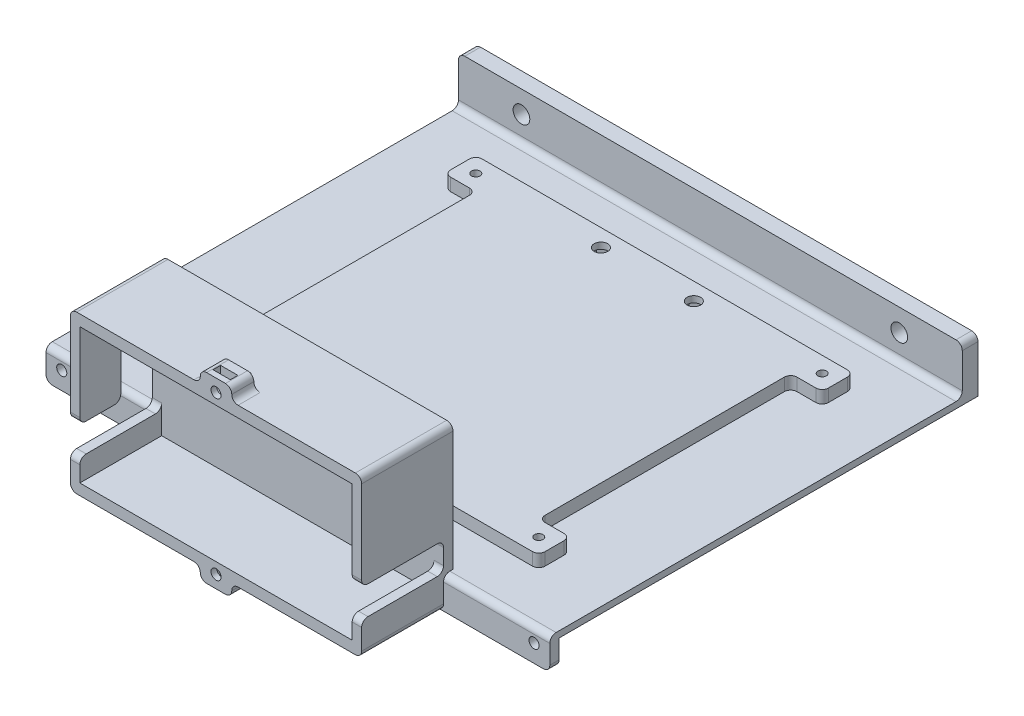
SolidWorks part; units mm, degrees
ref_plane "Front Plane" through (0, 0, 0) normal (0, 0, 1) x (1, 0, 0)
ref_plane "Top Plane" through (0, 0, 0) normal (0, 1, 0) x (1, 0, 0)
ref_plane "Right Plane" through (0, 0, 0) normal (1, 0, 0) x (0, 0, -1)
sketch "Sketch1" plane through (0, 0, 0) normal (0, 1, 0) x (1, 0, 0)
  line L1 (-80, -66.5) -> (80, -66.5)
  line L2 (-80, -66.5) -> (-80, 66.5)
  line L3 (-80, 66.5) -> (80, 66.5)
  line L4 (80, -66.5) -> (80, 66.5)
  line L5 (-80, -66.5) -> (80, 66.5) construction
  line L6 (-80, 66.5) -> (80, -66.5) construction
  point P0 (0, 0)
  dimension "D1" = 133
  dimension "D2" = 160
extrude "Boss-Extrude1" add sketch "Sketch1" along normal blind 2
sketch "Sketch2" plane through (0, 0, 66.5) normal (0, 0, 1) x (1, 0, 0)
  line L0 (75, -2.38) -> (-75, -2.38) construction
  line L1 (-80, 2) -> (80, 2)
  line L2 (-80, 2) -> (-80, -8)
  line L3 (-80, -8) -> (80, -8)
  line L4 (80, 2) -> (80, -8)
  line L6 (-80, 0) -> (80, 0) construction
  point P10 (0, -2.38)
  dimension "D1" = 2.38
  dimension "D2" = 150
  dimension "D3" = 10
extrude "Boss-Extrude2" add sketch "Sketch2" along normal blind 3
hole_wizard "M3 Clearance Hole1" positions "Sketch3" profile "Sketch4" hole size "M3" standard "ANSI Metric"
sketch "Sketch3" plane through (0, 0, 69.5) normal (0, 0, 1) x (1, 0, 0)
  point P0 (-75, -2.38)
  point P3 (75, -2.38)
sketch "Sketch4" plane through (-75, -2.38, 69.5) normal (1, 0, 0) x (0, -1, 0)
  line L0 (0, 0) -> (0, 13.3614)
  line L1 (0, 13.3614) -> (1.6, 12.4)
  line L2 (1.6, 12.4) -> (1.6, 0)
  line L5 (1.6, 0) -> (0, 0)
  line L10 (0, 13.3614) -> (-1.6, 12.4) construction
  line L11 (0, -6.35) -> (0, 107.95) construction
  dimension "Hole Dia." = 3.2
  dimension "Hole Depth" = 12.4
  dimension "Drill Angle" = 118
sketch "Sketch5" plane through (0, 0, -66.5) normal (0, 0, -1) x (-1, 0, 0)
  line L1 (-80, 2) -> (80, 2)
  line L2 (-80, 2) -> (-80, 17)
  line L3 (-80, 17) -> (80, 17)
  line L4 (80, 2) -> (80, 17)
  dimension "D1" = 15
extrude "Boss-Extrude3" add sketch "Sketch5" against normal blind 5
sketch "Sketch6" plane through (0, 0, -61.5) normal (0, 0, 1) x (1, 0, 0)
  line L0 (-60, 10) -> (60, 10) construction
  line L1 (80, 2) -> (-80, 2) construction
  point P1 (60, 10)
  point P2 (-60, 10)
  point P14 (0, 10)
  point P17 (-60, 10)
  point P19 (60, 10)
  dimension "D1" = 120
  dimension "D2" = 8
hole_wizard "M5 Clearance Hole1" positions "Sketch6" profile "Sketch7" hole size "M5" standard "ANSI Metric"
sketch "Sketch7" plane through (60, 10, -61.5) normal (1, 0, 0) x (0, -1, 0)
  line L0 (0, 0) -> (0, 13.9923)
  line L1 (0, 13.9923) -> (2.65, 12.4)
  line L2 (2.65, 12.4) -> (2.65, 0)
  line L5 (2.65, 0) -> (0, 0)
  line L10 (0, 13.9923) -> (-2.65, 12.4) construction
  line L11 (0, -6.35) -> (0, 107.95) construction
  dimension "Hole Dia." = 5.3
  dimension "Hole Depth" = 12.4
  dimension "Drill Angle" = 118
sketch "Sketch8" plane through (0, 2, 0) normal (0, 1, 0) x (1, 0, 0)
  line L0 (-50, 37) -> (-50, -43)
  line L1 (-14.75, -47.5) -> (14.75, -47.5) construction
  line L2 (-14.75, -47.5) -> (-14.75, 41.5) construction
  line L3 (-14.75, 41.5) -> (14.75, 41.5) construction
  line L4 (14.75, -47.5) -> (14.75, 41.5) construction
  line L5 (-14.75, -47.5) -> (14.75, 41.5) construction
  line L6 (-14.75, 41.5) -> (14.75, -47.5) construction
  line L7 (-50, -53) -> (50, -53)
  line L8 (-50, -53) -> (-50, 47) construction
  line L9 (-50, 47) -> (50, 47)
  line L10 (50, -53) -> (50, 47) construction
  line L11 (-50, -53) -> (50, 47) construction
  line L12 (-50, 47) -> (50, -53) construction
  line L13 (-50, 47) -> (-60, 47)
  line L14 (-50, 47) -> (-50, 37) construction
  line L15 (-50, 37) -> (-60, 37)
  line L16 (-60, 47) -> (-60, 37)
  line L17 (-50, -53) -> (-60, -53)
  line L18 (-50, -53) -> (-50, -43) construction
  line L19 (-50, -43) -> (-60, -43)
  line L20 (-60, -53) -> (-60, -43)
  line L21 (50, -53) -> (60, -53)
  line L22 (50, -53) -> (50, -43) construction
  line L23 (50, -43) -> (60, -43)
  line L24 (60, -53) -> (60, -43)
  line L25 (50, 47) -> (60, 47)
  line L26 (50, 47) -> (50, 37) construction
  line L27 (50, 37) -> (60, 37)
  line L28 (60, 47) -> (60, 37)
  line L29 (50, -43) -> (50, 37)
  line L31 (-55, -48) -> (55, -48) construction
  line L32 (-55, -48) -> (-55, 42) construction
  line L33 (-55, 42) -> (55, 42) construction
  line L34 (55, -48) -> (55, 42) construction
  line L35 (-55, -48) -> (55, 42) construction
  line L36 (-55, 42) -> (55, -48) construction
  point P0 (0, -3)
  point P5 (0, -3)
  point P6 (0, -3)
  dimension "D1" = 29.5
  dimension "D2" = 89
  dimension "D3" = 100
  dimension "D4" = 100
  dimension "D5" = 3
  dimension "D6" = 10
  dimension "D7" = 10
  dimension "D8" = 110
  dimension "D9" = 90
extrude "Boss-Extrude4" add sketch "Sketch8" along normal blind 4
hole_wizard "M2.5 Clearance Hole1" positions "Sketch23" profile "Sketch24" hole size "M2.5" standard "ANSI Metric" end condition through all
sketch "Sketch23" plane through (0, 6, 0) normal (0, 1, 0) x (1, 0, 0)
  point P0 (-55, 42)
  point P3 (55, 42)
  point P6 (55, -48)
  point P9 (-55, -48)
sketch "Sketch24" plane through (-55, 6, -42) normal (1, 0, 0) x (0, 0, 1)
  line L0 (0, 0) -> (0, 14)
  line L1 (0, 14) -> (1.35, 14)
  line L2 (1.35, 14) -> (1.35, 0)
  line L5 (1.35, 0) -> (0, 0)
  line L11 (0, -6.35) -> (0, 107.95) construction
  dimension "Thru Hole Dia." = 2.7
  dimension "Thru Hole Depth" = 14
hole_wizard "M4 Clearance Hole1" positions "Sketch9" profile "Sketch10" hole size "M4" standard "ANSI Metric" end condition through all
sketch "Sketch9" plane through (0, 6, 0) normal (0, 1, 0) x (1, 0, 0)
  point P0 (-14.75, 41.5)
  point P3 (14.75, 41.5)
  point P6 (-14.75, -47.5)
  point P9 (14.75, -47.5)
sketch "Sketch10" plane through (-14.75, 6, -41.5) normal (1, 0, 0) x (0, 0, 1)
  line L0 (0, 0) -> (0, 14)
  line L1 (0, 14) -> (2.15, 14)
  line L2 (2.15, 14) -> (2.15, 0)
  line L5 (2.15, 0) -> (0, 0)
  line L11 (0, -6.35) -> (0, 107.95) construction
  dimension "Thru Hole Dia." = 4.3
  dimension "Thru Hole Depth" = 14
sketch "Sketch25" plane through (0, 0, 0) normal (0, -1, 0) x (-1, 0, 0)
  line L1 (55, -50.8868) -> (57.5, -49.4434)
  line L2 (57.5, -49.4434) -> (57.5, -46.5566)
  line L3 (57.5, -46.5566) -> (55, -45.1132)
  line L4 (55, -45.1132) -> (52.5, -46.5566)
  line L5 (52.5, -46.5566) -> (52.5, -49.4434)
  line L6 (52.5, -49.4434) -> (55, -50.8868)
  line L7 (-55, -50.8868) -> (-52.5, -49.4434)
  line L8 (-52.5, -49.4434) -> (-52.5, -46.5566)
  line L9 (-52.5, -46.5566) -> (-55, -45.1132)
  line L10 (-55, -45.1132) -> (-57.5, -46.5566)
  line L11 (-57.5, -46.5566) -> (-57.5, -49.4434)
  line L12 (-57.5, -49.4434) -> (-55, -50.8868)
  line L13 (-55, 39.1132) -> (-52.5, 40.5566)
  line L14 (-52.5, 40.5566) -> (-52.5, 43.4434)
  line L15 (-52.5, 43.4434) -> (-55, 44.8868)
  line L16 (-55, 44.8868) -> (-57.5, 43.4434)
  line L17 (-57.5, 43.4434) -> (-57.5, 40.5566)
  line L18 (-57.5, 40.5566) -> (-55, 39.1132)
  line L19 (55, 39.1132) -> (57.5, 40.5566)
  line L20 (57.5, 40.5566) -> (57.5, 43.4434)
  line L21 (57.5, 43.4434) -> (55, 44.8868)
  line L22 (55, 44.8868) -> (52.5, 43.4434)
  line L23 (52.5, 43.4434) -> (52.5, 40.5566)
  line L24 (52.5, 40.5566) -> (55, 39.1132)
  line L25 (-14.75, 45.5415) -> (-18.25, 43.5207)
  line L26 (-18.25, 43.5207) -> (-18.25, 39.4793)
  line L27 (-18.25, 39.4793) -> (-14.75, 37.4585)
  line L28 (-14.75, 37.4585) -> (-11.25, 39.4793)
  line L29 (-11.25, 39.4793) -> (-11.25, 43.5207)
  line L30 (-11.25, 43.5207) -> (-14.75, 45.5415)
  line L31 (14.75, 45.5415) -> (11.25, 43.5207)
  line L32 (11.25, 43.5207) -> (11.25, 39.4793)
  line L33 (11.25, 39.4793) -> (14.75, 37.4585)
  line L34 (14.75, 37.4585) -> (18.25, 39.4793)
  line L35 (18.25, 39.4793) -> (18.25, 43.5207)
  line L36 (18.25, 43.5207) -> (14.75, 45.5415)
  line L37 (14.75, -43.4585) -> (11.25, -45.4793)
  line L38 (11.25, -45.4793) -> (11.25, -49.5207)
  line L39 (11.25, -49.5207) -> (14.75, -51.5415)
  line L40 (14.75, -51.5415) -> (18.25, -49.5207)
  line L41 (18.25, -49.5207) -> (18.25, -45.4793)
  line L42 (18.25, -45.4793) -> (14.75, -43.4585)
  line L43 (-14.75, -43.4585) -> (-18.25, -45.4793)
  line L44 (-18.25, -45.4793) -> (-18.25, -49.5207)
  line L45 (-18.25, -49.5207) -> (-14.75, -51.5415)
  line L46 (-14.75, -51.5415) -> (-11.25, -49.5207)
  line L47 (-11.25, -49.5207) -> (-11.25, -45.4793)
  line L48 (-11.25, -45.4793) -> (-14.75, -43.4585)
  circle A0 centre (55, -48) radius 2.5 construction
  circle A1 centre (-55, -48) radius 2.5 construction
  circle A2 centre (-55, 42) radius 2.5 construction
  circle A3 centre (55, 42) radius 2.5 construction
  circle A4 centre (-14.75, 41.5) radius 3.5 construction
  circle A5 centre (14.75, 41.5) radius 3.5 construction
  circle A6 centre (14.75, -47.5) radius 3.5 construction
  circle A7 centre (-14.75, -47.5) radius 3.5 construction
  dimension "D1" = 5
  dimension "D2" = 7
extrude "Cut-Extrude4" cut sketch "Sketch25" against normal offset from surface (4 mm away) 2 up to face at (-14.75, 6, -39.35)
sketch "Sketch13" plane through (0, -8, 0) normal (0, -1, 0) x (1, 0, 0)
  line L1 (-43.25, 69.5) -> (43.25, 69.5) construction
  line L2 (-43.25, 69.5) -> (-43.25, 95.5) construction
  line L3 (-43.25, 95.5) -> (43.25, 95.5) construction
  line L4 (43.25, 69.5) -> (43.25, 95.5) construction
  line L6 (-80, 69.5) -> (80, 69.5) construction
  line L7 (-80, 66.5) -> (80, 66.5) construction
  line L8 (-46.25, 66.5) -> (46.25, 66.5)
  line L9 (-46.25, 66.5) -> (-46.25, 95.5)
  line L10 (-46.25, 95.5) -> (46.25, 95.5)
  line L11 (46.25, 66.5) -> (46.25, 95.5)
  point P6 (0, 69.5)
  point P14 (0, 66.5)
  dimension "D1" = 86.5
  dimension "D2" = 26
  dimension "D3" = 3
extrude "Boss-Extrude5" add sketch "Sketch13" against normal blind 50
sketch "Sketch14" plane through (0, 0, 95.5) normal (0, 0, 1) x (1, 0, 0)
  line L0 (-46.25, 42) -> (46.25, -8) construction
  line L2 (-43.25, -4.5) -> (43.25, -4.5)
  line L3 (-43.25, -4.5) -> (-43.25, 38.5)
  line L4 (-43.25, 38.5) -> (43.25, 38.5)
  line L5 (43.25, -4.5) -> (43.25, 38.5)
  line L6 (-43.25, -4.5) -> (43.25, 38.5) construction
  line L7 (-43.25, 38.5) -> (43.25, -4.5) construction
  point P4 (0, 17)
  point P5 (0, 17)
  dimension "D1" = 86.5
  dimension "D2" = 43
extrude "Cut-Extrude1" cut sketch "Sketch14" against normal blind 26
sketch "Sketch15" plane through (0, 0, 95.5) normal (0, 0, 1) x (1, 0, 0)
  line L0 (0, -8) -> (0, 42) construction
  line L1 (0, 42) -> (0, 38.5) construction
  line L2 (46.25, 42) -> (-46.25, 42) construction
  line L3 (43.25, 38.5) -> (-43.25, 38.5) construction
  line L4 (-43.25, 38.5) -> (-43.25, -4.5) construction
  line L8 (46.25, -8) -> (-46.25, -8) construction
  line L9 (-5, 42) -> (5, 42)
  line L10 (-5, 42) -> (-5, 46)
  line L11 (-5, 46) -> (5, 46)
  line L12 (5, 42) -> (5, 46)
  line L13 (5, -8) -> (-5, -8)
  line L14 (5, -8) -> (5, -12)
  line L15 (5, -12) -> (-5, -12)
  line L16 (-5, -8) -> (-5, -12)
  point P4 (0, 17)
  point P14 (-43.25, 17)
  point P23 (0, -8)
  point P24 (0, 42)
  dimension "D1" = 4
  dimension "D2" = 10
extrude "Boss-Extrude6" add sketch "Sketch15" against normal blind 7
hole_wizard "Ø3.2 (3.2) Diameter Hole1" positions "Sketch18" profile "Sketch19" hole size "Ø3.2" standard "ANSI Metric"
sketch "Sketch18" plane through (0, 0, 95.5) normal (0, 0, 1) x (1, 0, 0)
  point P0 (0, 42)
  point P3 (0, -8)
sketch "Sketch19" plane through (0, 42, 95.5) normal (1, 0, 0) x (0, -1, 0)
  line L0 (0, 0) -> (0, 10.9614)
  line L1 (0, 10.9614) -> (1.6, 10)
  line L2 (1.6, 10) -> (1.6, 0)
  line L5 (1.6, 0) -> (0, 0)
  line L10 (0, 10.9614) -> (-1.6, 10) construction
  line L11 (0, -6.35) -> (0, 107.95) construction
  dimension "Hole Dia." = 3.2
  dimension "Hole Depth" = 10
  dimension "Drill Angle" = 118
sketch "Sketch20" plane through (0, 0, 95.5) normal (0, 0, 1) x (1, 0, 0)
  line L0 (-46.25, 42) -> (-46.25, -8) construction
  line L1 (-46.25, 11.5) -> (46.25, 11.5) construction
  line L2 (-46.25, 11.5) -> (-46.25, 2.5)
  line L3 (-46.25, 2.5) -> (46.25, 2.5)
  line L4 (46.25, 11.5) -> (46.25, 2.5)
  line L10 (-43.25, -4.5) -> (43.25, -4.5) construction
  line L11 (46.25, 42) -> (46.25, -8) construction
  line L12 (-43.25, 38.5) -> (-43.25, -4.5) construction
  line L13 (-46.25, 11.5) -> (-43.25, 11.5) construction
  line L14 (-46.25, 11.5) -> (-46.25, 32.5)
  line L15 (-46.25, 32.5) -> (-43.25, 32.5)
  line L16 (-43.25, 11.5) -> (-43.25, 32.5)
  line L17 (-43.25, 11.5) -> (46.25, 11.5)
  dimension "D1" = 16
  dimension "D2" = 7
  dimension "D3" = 30
extrude "Cut-Extrude2" cut sketch "Sketch20" against normal up to surface (26 mm away) up to face at (0, 17, 69.5)
sketch "Sketch21" plane through (-46.25, 0, 0) normal (-1, 0, 0) x (0, 0, 1)
  line L0 (69.5, 11.5) -> (95.5, 11.5) construction
  line L1 (95.5, 32.5) -> (82.5, 32.5)
  line L2 (95.5, 32.5) -> (95.5, 11.5)
  line L3 (95.5, 11.5) -> (82.5, 11.5)
  line L4 (82.5, 32.5) -> (82.5, 11.5)
  line L5 (69.5, 32.5) -> (95.5, 32.5) construction
  point P9 (82.5, 32.5)
extrude "Boss-Extrude7" add sketch "Sketch21" against normal up to surface (3 mm away) up to face at (-43.25, 35.5, 82.5)
ref_plane "Plane1" through (0, 0, 92.5) normal (0, 0, 1) x (1, 0, 0)
sketch "Sketch22" plane through (0, 0, 92.5) normal (0, 0, 1) x (1, 0, 0)
  line L0 (-2.75, 43.5877) -> (-2.75, 46)
  line L1 (0, 45.1754) -> (-2.75, 43.5877) construction
  line L2 (-2.75, 43.5877) -> (-2.75, 40.4123)
  line L3 (-2.75, 40.4123) -> (0, 38.8246)
  line L4 (0, 38.8246) -> (2.75, 40.4123)
  line L5 (2.75, 40.4123) -> (2.75, 43.5877)
  line L6 (2.75, 43.5877) -> (0, 45.1754) construction
  line L7 (0, -11.1754) -> (2.75, -9.5877) construction
  line L8 (2.75, -9.5877) -> (2.75, -6.4123)
  line L9 (2.75, -6.4123) -> (0, -4.8246)
  line L10 (0, -4.8246) -> (-2.75, -6.4123)
  line L11 (-2.75, -6.4123) -> (-2.75, -9.5877)
  line L12 (-2.75, -9.5877) -> (0, -11.1754) construction
  line L13 (5, 46) -> (-5, 46) construction
  line L14 (-2.75, 46) -> (2.75, 46)
  line L15 (2.75, 46) -> (2.75, 43.5877)
  line L16 (-2.75, -9.5877) -> (-2.75, -12)
  line L17 (-5, -12) -> (5, -12) construction
  line L18 (-2.75, -12) -> (2.75, -12)
  line L19 (2.75, -12) -> (2.75, -9.5877)
  circle A0 centre (0, 42) radius 2.75 construction
  circle A1 centre (0, -8) radius 2.75 construction
  dimension "D1" = 5.5
extrude "Cut-Extrude3" cut sketch "Sketch22" against normal mid plane 2.4
fillet "Fillet1" radius 2 41 edges at (-80, -8, 68) (80, -8, 68) (63.125, 2, 69.5) (-63.125, 2, 69.5) (-46.25, -8, 82.5) (46.25, -8, 82.5) (46.25, 42, 81) (-46.25, 42, 81) (80, 17, -64) (-80, 17, -64) (0, 2, -61.5) (-44.75, 2.5, 69.5) (-44.75, 2.5, 95.5) (44.75, 2.5, 95.5) (44.75, 2.5, 69.5) (44.75, 11.5, 69.5) (44.75, 11.5, 95.5) (-44.75, 32.5, 82.5) (-44.75, 11.5, 82.5) (-44.75, 11.5, 95.5) (-44.75, 32.5, 69.5) (60, 4, -47) (60, 4, -37) (50, 4, -37) (50, 4, 43) (60, 4, 43) (60, 4, 53) (-60, 4, 53) (-50, 4, 43) (-50, 4, -37) (-60, 4, -37) (-60, 4, -47) (-60, 4, 43) (5, -8, 92) (5, -12, 92) (-5, -8, 92) (-5, -12, 92) (-5, 42, 92) (-5, 46, 92) (5, 42, 92) (5, 46, 92)
